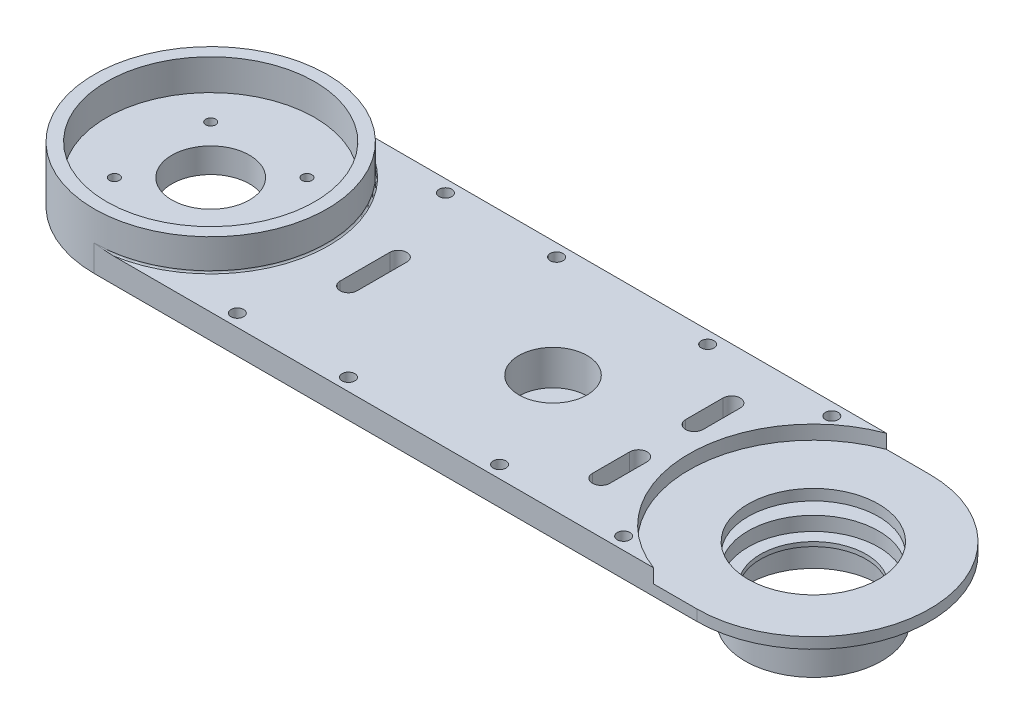
SolidWorks part; units mm, degrees
ref_plane "Front Plane" through (0, 0, 0) normal (0, 0, 1) x (1, 0, 0)
ref_plane "Top Plane" through (0, 0, 0) normal (0, 1, 0) x (1, 0, 0)
ref_plane "Right Plane" through (0, 0, 0) normal (1, 0, 0) x (0, 0, -1)
sketch "Sketch2" plane through (0, 0, 0) normal (0, 1, 0) x (1, 0, 0)
  line L0 (0, 0) -> (194, 0) construction
  line L1 (0, 37.5) -> (194, 37.5)
  line L2 (0, -37.5) -> (194, -37.5)
  line L3 (0, 0) -> (-15.4998, 15.4998) construction
  line L4 (0, 0) -> (0, 26.3985) construction
  line L5 (0, 0) -> (106.5, 0) construction
  line L6 (194, 0) -> (110.2, 0) construction
  arc A0 (0, 37.5) -> (0, -37.5) centre (0, 0) ccw
  arc A1 (194, -37.5) -> (194, 37.5) centre (194, 0) ccw
  circle A2 centre (0, 0) radius 12.5
  circle A3 centre (-15.4998, 15.4998) radius 1.6
  circle A4 centre (15.4998, 15.4998) radius 1.6
  circle A5 centre (15.4998, -15.4998) radius 1.6
  circle A6 centre (-15.4998, -15.4998) radius 1.6
  circle A7 centre (194, 0) radius 21
  circle A8 centre (194, 0) radius 30
  circle A9 centre (194, 0) radius 37.5 construction
  circle A10 centre (0, 0) radius 8 construction
  circle A11 centre (110.2, 0) radius 11
  point P19 (0, 0)
  dimension "D1" = 75
  dimension "D2" = 75
  dimension "D4" = 25
  dimension "D6" = 3.2
  dimension "D8" = 45
  dimension "D9" = 83.8
  dimension "D10" = 42
  dimension "D11" = 60
  dimension "D12" = 22
  dimension "D3" = 194
  dimension "D5" = 21.92
  dimension "D7" = 4
extrude "Boss-Extrude1" add sketch "Sketch2" against normal blind 8 contours L2 A1 L1 A0 A11 A8 A6 A5 A4 A3 A2 | A7 | A8 A7 | A11 | A2
sketch "Sketch3" plane through (0, 0, 0) normal (0, 1, 0) x (1, 0, 0)
  line L0 (0, 0) -> (194, 0) construction
  line L1 (52.4, 17.9653) -> (52.4, -17.9653) construction
  line L2 (194, 37.5) -> (0, 37.5)
  line L3 (0, -37.5) -> (194, -37.5)
  line L4 (194, 37.5) -> (0, 37.5)
  line L5 (0, -37.5) -> (194, -37.5)
  line L6 (146.7, 15) -> (146.7, -17.9653) construction
  line L7 (146.7, 21) -> (146.7, 9) construction
  line L8 (149.495, 21) -> (149.495, 9)
  line L9 (143.905, 21) -> (143.905, 9)
  line L10 (52.4, 8) -> (52.4, -8) construction
  line L11 (55.1335, 8) -> (55.1335, -8)
  line L12 (49.6665, 8) -> (49.6665, -8)
  line L13 (146.7, -21) -> (146.7, -9) construction
  line L14 (149.495, -21) -> (149.495, -9)
  line L15 (143.905, -21) -> (143.905, -9)
  arc A0 (149.495, 21) -> (143.905, 21) centre (146.7, 21) ccw
  circle A1 centre (194, 0) radius 21
  circle A2 centre (194, 0) radius 21
  circle A3 centre (15.4998, -15.4998) radius 1.6
  circle A4 centre (15.4998, -15.4998) radius 1.6
  circle A5 centre (15.4998, 15.4998) radius 1.6
  circle A6 centre (15.4998, 15.4998) radius 1.6
  circle A7 centre (-15.4998, 15.4998) radius 1.6
  circle A8 centre (-15.4998, 15.4998) radius 1.6
  circle A9 centre (0, 0) radius 12.5
  circle A10 centre (0, 0) radius 12.5
  circle A11 centre (110.2, 0) radius 11
  arc A12 (194, -37.5) -> (194, 37.5) centre (194, 0) ccw
  arc A13 (0, 37.5) -> (0, -37.5) centre (0, 0) ccw
  arc A14 (194, -37.5) -> (194, 37.5) centre (194, 0) ccw
  arc A15 (0, 37.5) -> (0, -37.5) centre (0, 0) ccw
  circle A16 centre (110.2, 0) radius 11
  circle A17 centre (194, 0) radius 30
  circle A18 centre (194, 0) radius 30
  circle A19 centre (-15.4998, -15.4998) radius 1.6
  circle A20 centre (-15.4998, -15.4998) radius 1.6
  arc A21 (143.905, 9) -> (149.495, 9) centre (146.7, 9) ccw
  arc A22 (55.1335, 8) -> (49.6665, 8) centre (52.4, 8) ccw
  arc A23 (49.6665, -8) -> (55.1335, -8) centre (52.4, -8) ccw
  arc A24 (149.495, -21) -> (143.905, -21) centre (146.7, -21) cw
  arc A25 (143.905, -9) -> (149.495, -9) centre (146.7, -9) cw
  point P36 (146.7, 15)
  point P42 (52.4, 0)
  point P51 (146.7, -15)
  dimension "D10" = 52.4
  dimension "D11" = 36.5
  dimension "D12" = 16
  dimension "D13" = 12
  dimension "D14" = 15
  dimension "D1" = 0
  dimension "D2" = 0
  dimension "D3" = 0
  dimension "D4" = 0
  dimension "D5" = 0
  dimension "D6" = 0
  dimension "D7" = 0
  dimension "D8" = 0
  dimension "D9" = 0
extrude "Cut-Extrude1" cut sketch "Sketch3" against normal blind 8 contours A10 | L12 A23 L11 A22 | A25 L15 A24 L14 | L8 A21 L9 A0
sketch "Sketch4" plane through (0, 0, 0) normal (0, 1, 0) x (1, 0, 0)
  line L2 (194, 37.5) -> (0, 37.5)
  line L3 (0, -37.5) -> (194, -37.5)
  line L4 (194, 37.5) -> (0, 37.5)
  line L5 (0, -37.5) -> (194, -37.5)
  circle A0 centre (110.2, 0) radius 13
  circle A1 centre (194, 0) radius 21
  circle A2 centre (194, 0) radius 21
  circle A3 centre (15.4998, -15.4998) radius 1.6
  circle A4 centre (15.4998, -15.4998) radius 1.6
  circle A5 centre (15.4998, 15.4998) radius 1.6
  circle A6 centre (15.4998, 15.4998) radius 1.6
  circle A7 centre (-15.4998, 15.4998) radius 1.6
  circle A8 centre (-15.4998, 15.4998) radius 1.6
  circle A9 centre (0, 0) radius 12.5
  circle A10 centre (0, 0) radius 12.5
  circle A11 centre (110.2, 0) radius 11
  arc A12 (194, -37.5) -> (194, 37.5) centre (194, 0) ccw
  arc A13 (0, 37.5) -> (0, -37.5) centre (0, 0) ccw
  arc A14 (194, -37.5) -> (194, 37.5) centre (194, 0) ccw
  arc A15 (0, 37.5) -> (0, -37.5) centre (0, 0) ccw
  circle A16 centre (110.2, 0) radius 11 construction
  circle A17 centre (194, 0) radius 30
  circle A18 centre (194, 0) radius 30
  circle A19 centre (-15.4998, -15.4998) radius 1.6
  circle A20 centre (-15.4998, -15.4998) radius 1.6
  dimension "D10" = 26
  dimension "D1" = 0
  dimension "D2" = 0
  dimension "D3" = 0
  dimension "D4" = 0
  dimension "D5" = 0
  dimension "D6" = 0
  dimension "D7" = 0
  dimension "D8" = 0
  dimension "D9" = 0
extrude "Boss-Extrude2" add sketch "Sketch4" along normal blind 12.3 contours A0
sketch "Sketch5" plane through (0, 12.3, 0) normal (0, 1, 0) x (1, 0, 0)
  circle A0 centre (110.2, 0) radius 11
  dimension "D1" = 22
extrude "Cut-Extrude2" cut sketch "Sketch5" against normal blind 7
sketch "Sketch7" plane through (0, 5.3, 0) normal (0, 1, 0) x (1, 0, 0)
  circle A0 centre (110.2, 0) radius 4
  dimension "D1" = 8
extrude "Cut-Extrude3" cut sketch "Sketch7" against normal through all
sketch "Sketch8" plane through (0, 5.3, 0) normal (0, 1, 0) x (1, 0, 0)
  circle A1 centre (110.2, 0) radius 4
  circle A2 centre (110.2, 0) radius 13
  dimension "D1" = 26
  dimension "D2" = 8
extrude "Boss-Extrude4" add sketch "Sketch8" against normal blind 9
sketch "Sketch9" plane through (0, -8, 0) normal (0, -1, 0) x (1, 0, 0)
  circle A0 centre (110.2, 0) radius 11
  circle A1 centre (110.2, 0) radius 4
  dimension "D1" = 8
  dimension "D2" = 22
ref_plane "Plane1" through (0, -4, 0) normal (0, 1, 0) x (1, 0, 0)
mirror "Mirror2" about plane through (0, -4, 0) normal (0, 1, 0) of "Cut-Extrude3", "Cut-Extrude2", "Boss-Extrude2"
sketch "Sketch11" plane through (0, 12.3, 0) normal (0, 1, 0) x (1, 0, 0)
  circle A0 centre (110.2, 0) radius 13
extrude "Cut-Extrude7" cut sketch "Sketch11" against normal blind 12.3
sketch "Sketch12" plane through (0, 0, 0) normal (0, 1, 0) x (1, 0, 0)
  circle A0 centre (110.2, 0) radius 11
  circle A1 centre (110.2, 0) radius 4
  dimension "D1" = 22
extrude "Cut-Extrude8" cut sketch "Sketch12" against normal blind 11.3
sketch "Sketch13" plane through (0, 0, 0) normal (0, 1, 0) x (1, 0, 0)
  line L2 (194, 37.5) -> (0, 37.5)
  line L3 (0, -37.5) -> (194, -37.5)
  line L4 (194, 37.5) -> (0, 37.5)
  line L5 (0, -37.5) -> (194, -37.5)
  circle A0 centre (194, 0) radius 40
  circle A1 centre (194, 0) radius 21
  circle A2 centre (194, 0) radius 21
  circle A3 centre (15.4998, -15.4998) radius 1.6
  circle A4 centre (15.4998, -15.4998) radius 1.6
  circle A5 centre (15.4998, 15.4998) radius 1.6
  circle A6 centre (15.4998, 15.4998) radius 1.6
  circle A7 centre (-15.4998, 15.4998) radius 1.6
  circle A8 centre (-15.4998, 15.4998) radius 1.6
  circle A9 centre (0, 0) radius 12.5
  circle A10 centre (0, 0) radius 12.5
  circle A11 centre (110.2, 0) radius 11
  arc A12 (194, -37.5) -> (194, 37.5) centre (194, 0) ccw
  arc A13 (0, 37.5) -> (0, -37.5) centre (0, 0) ccw
  arc A14 (194, -37.5) -> (194, 37.5) centre (194, 0) ccw
  arc A15 (0, 37.5) -> (0, -37.5) centre (0, 0) ccw
  circle A16 centre (110.2, 0) radius 11
  circle A17 centre (194, 0) radius 30
  circle A18 centre (194, 0) radius 30 construction
  circle A19 centre (-15.4998, -15.4998) radius 1.6
  circle A20 centre (-15.4998, -15.4998) radius 1.6
  dimension "D10" = 80
  dimension "D1" = 0
  dimension "D2" = 0
  dimension "D3" = 0
  dimension "D4" = 0
  dimension "D5" = 0
  dimension "D6" = 0
  dimension "D7" = 0
  dimension "D8" = 0
  dimension "D9" = 0
extrude "Cut-Extrude9" cut sketch "Sketch13" against normal blind 4.5 contours A0
sketch "Sketch14" plane through (0, -4.5, 0) normal (0, 1, 0) x (1, 0, 0)
  circle A0 centre (194, 0) radius 21
  dimension "D1" = 42
extrude "Cut-Extrude10" cut sketch "Sketch14" against normal through all
sketch "Sketch15" plane through (0, -8, 0) normal (0, -1, 0) x (1, 0, 0)
  line L0 (194, 21) -> (194, -21) construction
  line L1 (173, 0) -> (215, 0) construction
  circle A0 centre (194, 0) radius 21 construction
ref_plane "Plane2" through (194, 0, 0) normal (1, 0, 0) x (0, 0, -1)
sketch "Sketch16" plane through (194, 0, 0) normal (1, 0, 0) x (0, 0, -1)
  line L0 (0, -8) -> (-29, -8)
  line L1 (-21, -8) -> (21, -8) construction
  line L2 (-29, -8) -> (-29, -12)
  line L3 (-29, -12) -> (-21, -12)
  line L4 (-21, -12) -> (-21, -16.5)
  line L5 (-21, -16.5) -> (-17, -16.5)
  line L6 (-17, -16.5) -> (-17, -17.9)
  line L7 (-17, -17.9) -> (-21, -17.9)
  line L8 (-21, -17.9) -> (-21, -26.8048)
  line L9 (0, -7) -> (-30, -7) construction
  line L10 (0, -8) -> (0, -28.9148) construction
  line L11 (-30, -13) -> (-30, -8)
  line L12 (-30, -13) -> (-22, -13)
  line L13 (-22, -13) -> (-22, -17.2)
  line L14 (-22, -17.2) -> (-22, -17.2)
  line L15 (-22, -17.2) -> (-22, -17.2)
  line L16 (-22, -17.2) -> (-22, -17.2)
  line L17 (-22, -17.2) -> (-22, -26.8048)
  line L18 (-30, -7) -> (-30, -13) construction
  line L19 (-30, -8) -> (-29, -8)
  line L20 (-22, -26.8048) -> (-21, -26.8048)
  dimension "D1" = 29
  dimension "D2" = 4
  dimension "D3" = 8.5
  dimension "D4" = 21
  dimension "D5" = 1.4
  dimension "D6" = 4
  dimension "D7" = 1
revolve "Revolve1" add sketch "Sketch16" angle 360 about L10
sketch "Sketch17" plane through (0, 0, 0) normal (0, 1, 0) x (1, 0, 0)
  circle A0 centre (0, 0) radius 37.5
  circle A1 centre (0, 0) radius 33.5
  dimension "D1" = 75
  dimension "D2" = 4
extrude "Boss-Extrude5" add sketch "Sketch17" along normal blind 10
fillet "Fillet1" radius 0.5 1 edges at (37.5, 0, 0)
sketch "Sketch18" plane through (0, -8, 0) normal (0, -1, 0) x (1, 0, 0)
  line L0 (0, 37.5) -> (194, 37.5) construction
  line L1 (0, -37.5) -> (194, -37.5) construction
  line L2 (0, 37.5) -> (194, 37.5) construction
  line L3 (0, -37.5) -> (194, -37.5) construction
  line L4 (0, 33.5) -> (194, 33.5) construction
  line L5 (0, -33.5) -> (194, -33.5) construction
  line L6 (-33.5, 0) -> (227.5, 0) construction
  arc A0 (194, -37.5) -> (194, 37.5) centre (194, 0) ccw construction
  arc A1 (0, 37.5) -> (0, -37.5) centre (0, 0) ccw construction
  arc A2 (194, -37.5) -> (194, 37.5) centre (194, 0) ccw construction
  arc A3 (0, 37.5) -> (0, -37.5) centre (0, 0) ccw construction
  arc A4 (194, -33.5) -> (194, 33.5) centre (194, 0) ccw construction
  arc A5 (0, 33.5) -> (0, -33.5) centre (0, 0) ccw construction
  circle A6 centre (42.07, 33.5) radius 2.05
  circle A7 centre (-12.7191, 30.9915) radius 2.05
  circle A8 centre (126.4882, 33.5) radius 2.05
  circle A9 centre (166.4458, 33.5) radius 2.05
  circle A10 centre (-33.5, 0) radius 2.05
  circle A11 centre (77.8531, 33.5) radius 2.05
  circle A12 centre (166.4458, -33.5) radius 2.05
  circle A13 centre (126.4882, -33.5) radius 2.05
  circle A14 centre (77.8531, -33.5) radius 2.05
  circle A15 centre (42.07, -33.5) radius 2.05
  circle A16 centre (-12.7191, -30.9915) radius 2.05
  dimension "D2" = 4.1
  dimension "D3" = 4.1
  dimension "D4" = 4.1
  dimension "D1" = 4
extrude "Cut-Extrude11" cut sketch "Sketch18" against normal blind 8 contours A7 | A6 | A11 | A8 | A9 | A10 | A16 | A15 | A14 | A13 | A12
sketch "Sketch19" plane through (0, 0, 0) normal (0, -1, 0) x (1, 0, 0)
  circle A0 centre (-33.5, 0) radius 2.05
  arc A1 (-33.4373, 2.049) -> (-33.4373, -2.049) centre (0, 0) ccw construction
  circle A2 centre (-12.7191, 30.9915) radius 2.05
  arc A3 (-10.7997, 31.7115) -> (-14.5909, 30.1555) centre (0, 0) ccw construction
  circle A4 centre (-12.7191, -30.9915) radius 2.05
  arc A5 (-14.5909, -30.1555) -> (-10.7997, -31.7115) centre (0, 0) ccw construction
extrude "Boss-Extrude6" add sketch "Sketch19" along normal blind 1
